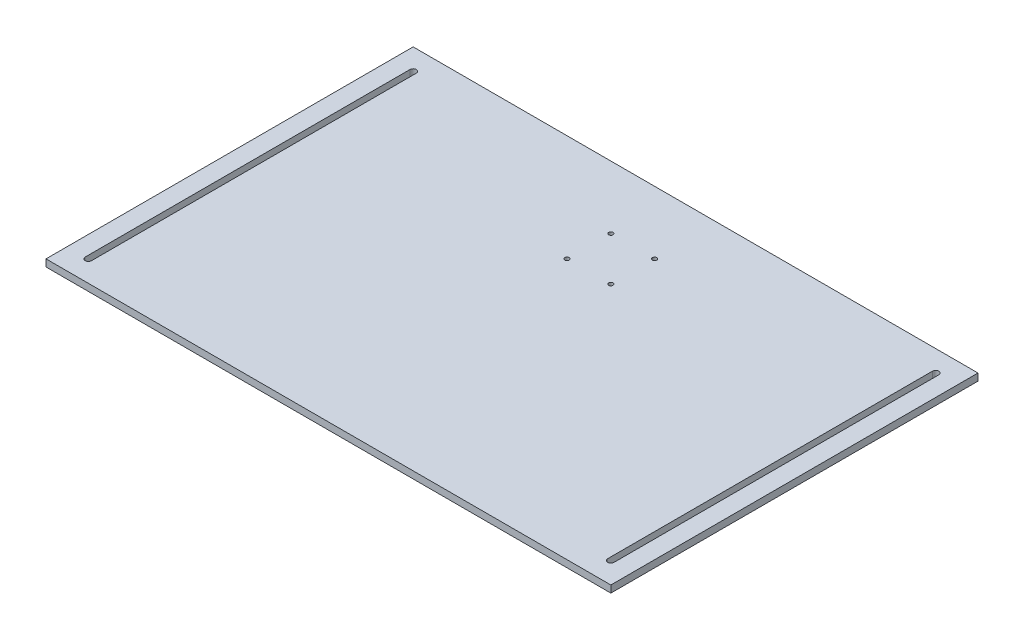
SolidWorks part; units mm, degrees
ref_plane "前基準面" through (0, 0, 0) normal (0, 0, 1) x (1, 0, 0)
ref_plane "上基準面" through (0, 0, 0) normal (0, 1, 0) x (1, 0, 0)
ref_plane "右基準面" through (0, 0, 0) normal (1, 0, 0) x (0, 0, -1)
sketch "草圖1" plane through (0, 0, 0) normal (0, 1, 0) x (1, 0, 0)
  line L0 (200, 60) -> (170, 60) construction
  line L1 (200, 160) -> (-200, 160) construction
  line L2 (200, 160) -> (200, -160) construction
  line L3 (200, -160) -> (-200, -160) construction
  line L4 (-200, 160) -> (-200, -160) construction
  line L5 (0, -160) -> (0, 160) construction
  line L6 (200, 0) -> (-200, 0) construction
  line L7 (-200, 160) -> (200, 160) construction
  line L8 (-200, 160) -> (-200, 130) construction
  line L9 (-200, 130) -> (200, 130) construction
  line L10 (200, 160) -> (200, 130) construction
  line L11 (-200, 130) -> (-170, 130) construction
  line L12 (-200, 130) -> (-200, -130) construction
  line L13 (-200, -130) -> (-170, -130) construction
  line L14 (-170, 130) -> (-170, -130) construction
  line L15 (200, -160) -> (-200, -160) construction
  line L16 (200, -160) -> (200, -130) construction
  line L17 (200, -130) -> (-200, -130) construction
  line L18 (-200, -160) -> (-200, -130) construction
  line L19 (200, -130) -> (170, -130) construction
  line L20 (200, -130) -> (200, 130) construction
  line L21 (200, 130) -> (170, 130) construction
  line L22 (170, -130) -> (170, 130) construction
  line L23 (-200, 130) -> (-170, 130) construction
  line L24 (-200, 130) -> (-200, 60) construction
  line L25 (-200, 60) -> (-170, 60) construction
  line L26 (-170, 130) -> (-170, 60) construction
  line L27 (170, 130) -> (170, 60) construction
  line L29 (200, 130) -> (200, 60) construction
  line L30 (-200, -60) -> (-170, -60) construction
  line L31 (-170, -130) -> (-170, -60) construction
  line L32 (-200, -130) -> (-170, -130) construction
  line L33 (-200, -130) -> (-200, -60) construction
  line L34 (200, -130) -> (200, -60) construction
  line L35 (170, -130) -> (170, -60) construction
  line L36 (200, -60) -> (170, -60) construction
  line L37 (200, -130) -> (170, -130) construction
  line L40 (-200, 130) -> (-200, -130)
  line L42 (200, 130) -> (200, -130)
  line L43 (-200, 130) -> (200, 130)
  line L44 (-200, 130) -> (-200, -130)
  line L45 (-200, -130) -> (200, -130)
  line L46 (200, 130) -> (200, -130)
  point P0 (0, 0)
  dimension "D1" = 400
  dimension "D2" = 320
  dimension "D4" = 30
  dimension "D6" = 30
  dimension "D7" = 70
extrude "填料-伸長1" add sketch "草圖1" along normal blind 5 contours L40 L45 L42 L43 region at (0, 0, 0)
sketch "草圖2" plane through (0, 5, 0) normal (0, 1, 0) x (1, 0, 0)
  line L0 (-185, 130) -> (-185, -130) construction
  line L1 (-200, 130) -> (200, 130) construction
  line L2 (-200, -130) -> (200, -130) construction
  line L3 (185, -130) -> (185, 130) construction
  line L4 (-185, 115) -> (-185, -115) construction
  line L5 (-182.75, 115) -> (-182.75, -115)
  line L6 (-187.25, 115) -> (-187.25, -115)
  line L7 (-200, 60) -> (-170, 60) construction
  line L8 (200, 0) -> (-200, 0) construction
  line L9 (0, -160) -> (0, 160) construction
  line L10 (0, -160) -> (0, 160) construction
  line L11 (185, 115) -> (185, -115) construction
  line L12 (182.75, 115) -> (182.75, -115)
  line L13 (187.25, 115) -> (187.25, -115)
  arc A0 (-182.75, 115) -> (-187.25, 115) centre (-185, 115) ccw
  arc A1 (-187.25, -115) -> (-182.75, -115) centre (-185, -115) ccw
  arc A2 (182.75, 115) -> (187.25, 115) centre (185, 115) cw
  arc A3 (187.25, -115) -> (182.75, -115) centre (185, -115) cw
  point P10 (-185, 0)
  point P17 (-185, 60)
  point P25 (185, 0)
  dimension "D1" = 4.5
  dimension "D2" = 230
extrude "除料-伸長1" cut sketch "草圖2" against normal through all
sketch "草圖3" plane through (0, 5, 0) normal (0, 1, 0) x (1, 0, 0)
  line L0 (0, -160) -> (0, 160) construction
  line L5 (-200, 130) -> (-200, -130) construction
  line L10 (-200, 190) -> (200, 190) construction
  line L11 (-200, 190) -> (-200, 130) construction
  line L12 (-200, 130) -> (200, 130) construction
  line L13 (-21.15, 85.5) -> (-15.5, 91.15) construction
  line L14 (-15.5, 91.15) -> (15.5, 91.15) construction
  line L15 (-21.15, 85.5) -> (-21.15, 54.5) construction
  line L16 (-15.5, 48.85) -> (15.5, 48.85) construction
  line L17 (21.15, 85.5) -> (21.15, 54.5) construction
  line L18 (15.5, 91.15) -> (21.15, 85.5) construction
  line L19 (15.5, 48.85) -> (21.15, 54.5) construction
  line L20 (-21.15, 54.5) -> (-15.5, 48.85) construction
  line L21 (200, 190) -> (200, 130) construction
  circle A4 centre (-15.5, 85.5) radius 1.55
  circle A5 centre (15.5, 85.5) radius 1.55
  circle A6 centre (-15.5, 54.5) radius 1.55
  circle A7 centre (15.5, 54.5) radius 1.55
  point P0 (0, 70)
  point P1 (0, 0)
  point P10 (0, 70)
  point P11 (0, 0)
  point P12 (0, 0)
  point P13 (0, 0)
  point P14 (0, 0)
  point P15 (0, 0)
  point P32 (0, 91.15)
  point P50 (-21.15, 70)
  dimension "D2" = 42.3
  dimension "D10" = 45
  dimension "D5" = 3.1
  dimension "D1" = 42.3
  dimension "D3" = 31
  dimension "D4" = 31
  dimension "D7" = 5.65
  dimension "D8" = 60
  dimension "D9" = 60
  dimension "D6" = 5.65
extrude "除料-伸長2" cut sketch "草圖3" against normal through all
